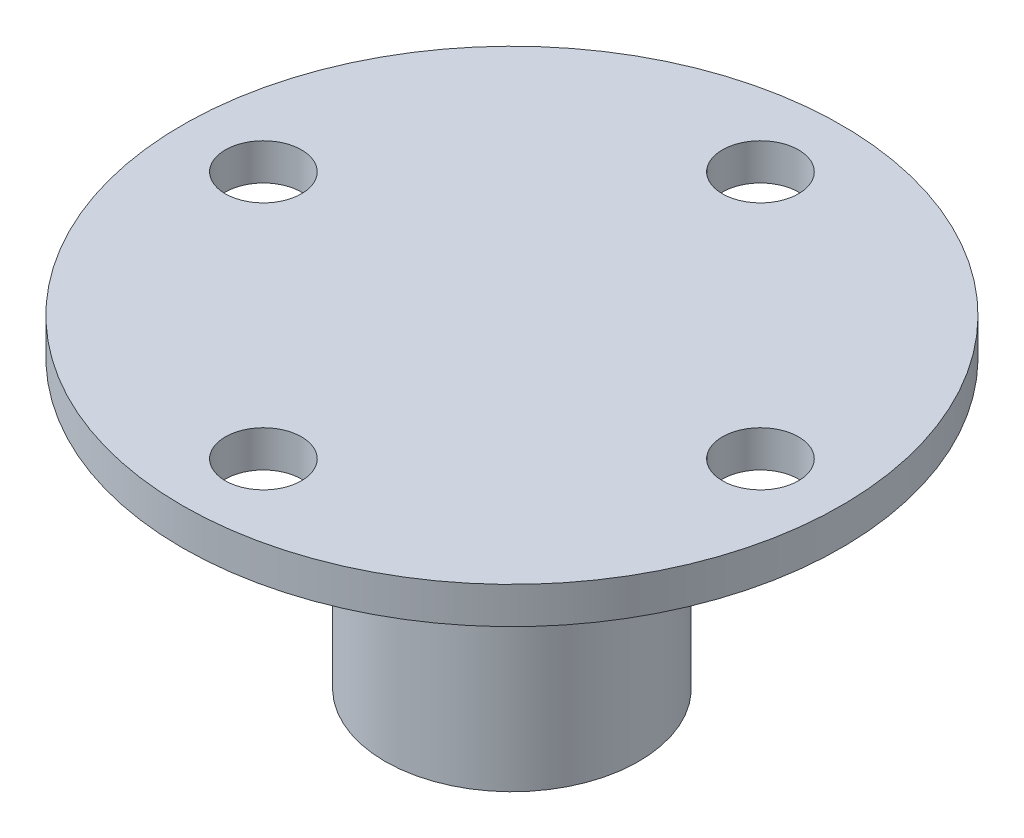
SolidWorks part; units mm, degrees
ref_plane "Front Plane" through (0, 0, 0) normal (0, 0, 1) x (1, 0, 0)
ref_plane "Top Plane" through (0, 0, 0) normal (0, 1, 0) x (1, 0, 0)
ref_plane "Right Plane" through (0, 0, 0) normal (1, 0, 0) x (0, 0, -1)
sketch "Sketch1" plane through (0, 0, 0) normal (0, 1, 0) x (1, 0, 0)
  line L0 (0, 0) -> (21.548, 0)
  line L6 (-6.7175, -3.8891) -> (-3.8891, -6.7175)
  line L7 (-3.8891, -6.7175) -> (-2.5858, -5.4142)
  line L8 (-6.7175, -3.8891) -> (-5.4142, -2.5858)
  circle A0 centre (0, 0) radius 28.575
  circle A1 centre (0, 0) radius 11
  circle A2 centre (21.548, 0) radius 3.302
  circle A3 centre (0, 0) radius 6
  circle A4 centre (0, -21.548) radius 3.302
  circle A5 centre (-21.548, 0) radius 3.302
  circle A6 centre (0, 21.548) radius 3.302
  point P20 (0, 0)
  dimension "D1" = 6.604
  dimension "D2" = 4
  dimension "D3" = 12
  dimension "D4" = 4
extrude "Boss-Extrude1" add sketch "Sketch1" along normal blind 3.175 contours A0 A6 A5 A4 A2 A1 region at (-27.7668, 0, 0)
extrude "Boss-Extrude2" add sketch "Sketch1<4>" along normal blind 3.175 contours A3 | A3 L8 L6 L7 | A3 A1 L7 L6 L8 region at (-10.6889, 0, 0) region at (3.1099, 0, 4.9316) region at (-4.7307, 0, 4.7307)
sketch "Sketch1<4>" plane through (0, 0, 0) normal (0, 1, 0) x (1, 0, 0) same geometry as "Sketch1"
extrude "Boss-Extrude3" add sketch "Sketch1<5>" against normal blind 24.825 contours A3 A1 L7 L6 L8 region at (-10.6889, 0, 0)
sketch "Sketch1<5>" plane through (0, 0, 0) normal (0, 1, 0) x (1, 0, 0) same geometry as "Sketch1"
fillet "Fillet1" radius 5 1 edges at (0, 0, 11)
